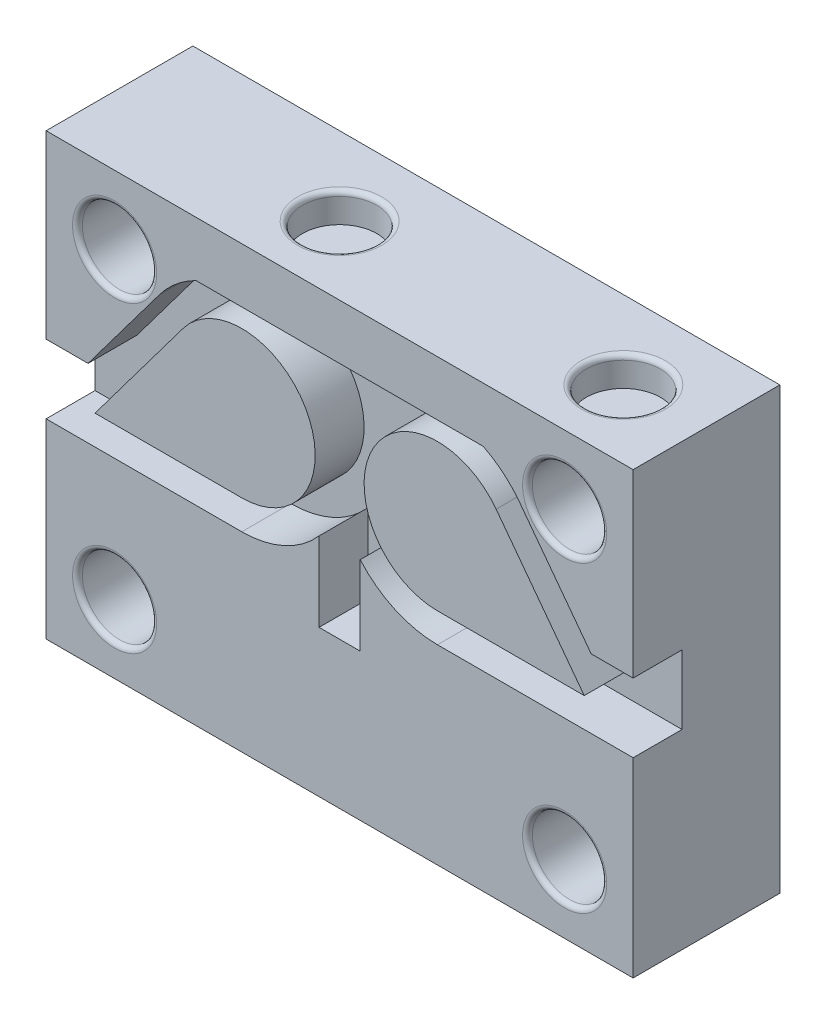
SolidWorks part; units mm, degrees
ref_plane "Front Plane" through (0, 0, 0) normal (0, 0, 1) x (1, 0, 0)
ref_plane "Top Plane" through (0, 0, 0) normal (0, 1, 0) x (1, 0, 0)
ref_plane "Right Plane" through (0, 0, 0) normal (1, 0, 0) x (0, 0, -1)
sketch "Sketch1" plane through (0, 0, 0) normal (0, 0, 1) x (1, 0, 0)
  line L0 (-37.3657, 7.5) -> (34.9105, 7.5) construction
  line L1 (-90, -22.5) -> (30, -22.5)
  line L2 (-30, -22.5) -> (-30, 22.5)
  line L3 (-30, 22.5) -> (30, 22.5)
  line L4 (30, -22.5) -> (30, 22.5)
  line L5 (-30, -22.5) -> (30, 22.5) construction
  line L6 (-30, 22.5) -> (30, -22.5) construction
  line L7 (-10, 29.4537) -> (-10, -35.1207) construction
  line L8 (0, 22.5) -> (0, -27.0967) construction
  line L9 (-10, 0) -> (-25, 0)
  line L10 (-25, 0) -> (-16, 12)
  line L11 (25, 0) -> (16, 12)
  line L12 (10, 0) -> (25, 0)
  line L13 (-50, -3) -> (-10, -3)
  line L15 (2.1006, 0.5827) -> (2.1003, -7.5128)
  line L16 (30, -16.875) -> (30, -3)
  line L17 (10, -3) -> (30, -3)
  line L18 (-10, -3) -> (-50, -3)
  line L19 (-2.1006, 0.5827) -> (-2.1006, -7.5128)
  line L20 (-2.1006, -7.5128) -> (2.1003, -7.5128)
  line L21 (-34.2857, 4.0476) -> (-25.7143, 4.0476)
  line L30 (-25.7143, 4.0476) -> (-18.4, 13.8)
  line L31 (-14.6784, 22.5) -> (-14.6784, 16.9001)
  line L32 (30, 4.0476) -> (25.7143, 4.0476)
  line L33 (25.7143, 4.0476) -> (18.4, 13.8)
  line L34 (14.6784, 22.5) -> (14.6784, 16.9001)
  line L35 (-14.6784, 16.9001) -> (14.6784, 16.9001)
  line L36 (-90, 0) -> (30, 0) construction
  line L37 (-60, 22.5) -> (-60, -27.0967) construction
  line L38 (-50, 29.4537) -> (-50, -35.1207) construction
  line L39 (-30, 22.5) -> (-90, -22.5) construction
  line L40 (-30, -22.5) -> (-90, 22.5) construction
  line L41 (-22.6343, 7.5) -> (-94.9105, 7.5) construction
  line L42 (-45.3216, 16.9001) -> (-74.6784, 16.9001)
  line L43 (-74.6784, 22.5) -> (-74.6784, 16.9001)
  line L44 (-85.7143, 4.0476) -> (-78.4, 13.8)
  line L45 (-90, 4.0476) -> (-85.7143, 4.0476)
  line L46 (-45.3216, 22.5) -> (-45.3216, 16.9001)
  line L47 (-34.2857, 4.0476) -> (-41.6, 13.8)
  line L48 (-57.8994, -7.5128) -> (-62.1003, -7.5128)
  line L49 (-57.8994, 0.5827) -> (-57.8994, -7.5128)
  line L50 (-70, -3) -> (-90, -3)
  line L51 (-90, -16.875) -> (-90, -3)
  line L52 (-62.1006, 0.5827) -> (-62.1003, -7.5128)
  line L53 (-70, 0) -> (-85, 0)
  line L54 (-85, 0) -> (-76, 12)
  line L55 (-35, 0) -> (-44, 12)
  line L56 (-50, 0) -> (-35, 0)
  line L57 (-90, -22.5) -> (-90, 22.5)
  line L58 (-30, 22.5) -> (-90, 22.5)
  circle A0 centre (-10, 7.5) radius 7.5
  circle A1 centre (10, 7.5) radius 7.5
  arc A2 (2.1006, 0.5827) -> (10, -3) centre (10, 7.5) ccw
  arc A3 (-2.1006, 0.5827) -> (-10, -3) centre (-10, 7.5) cw
  arc A4 (-18.4, 13.8) -> (-14.6784, 16.9001) centre (-10, 7.5) cw
  arc A5 (18.4, 13.8) -> (14.6784, 16.9001) centre (10, 7.5) ccw
  circle A6 centre (-23, 15.5) radius 3.8
  circle A7 centre (23, 15.5) radius 3.8
  circle A8 centre (23, -15.5) radius 3.8
  circle A9 centre (-23, -15.5) radius 3.8
  circle A10 centre (-37, -15.5) radius 3.8
  circle A11 centre (-83, -15.5) radius 3.8
  circle A12 centre (-83, 15.5) radius 3.8
  circle A13 centre (-37, 15.5) radius 3.8
  arc A14 (-78.4, 13.8) -> (-74.6784, 16.9001) centre (-70, 7.5) cw
  arc A15 (-41.6, 13.8) -> (-45.3216, 16.9001) centre (-50, 7.5) ccw
  arc A16 (-57.8994, 0.5827) -> (-50, -3) centre (-50, 7.5) ccw
  arc A17 (-62.1006, 0.5827) -> (-70, -3) centre (-70, 7.5) cw
  circle A18 centre (-70, 7.5) radius 7.5
  circle A19 centre (-50, 7.5) radius 7.5
  point P0 (0, 0)
  point P53 (-30, 0)
  point P86 (-30, 4.0476)
  point P90 (-30, -3)
  point P96 (-60, 0)
  dimension "D5" = 15
  dimension "D8" = 10.5
  dimension "D24" = 15.3216
  dimension "D7" = 7.6
  dimension "D2" = 45
  dimension "D3" = 15
  dimension "D4" = 20
  dimension "D6" = 15
  dimension "D9" = 7
  dimension "D10" = 7
  dimension "D11" = 60
  dimension "D12" = 4.2009
  dimension "D13" = 8.0954
  dimension "D20" = 3
  dimension "D21" = 10.5
  dimension "D23" = 4.2857
extrude "Boss-Extrude3" add sketch "Sketch1" along normal blind 15 contours L30 A4 L31 L3 L2 L21 A6 | L31 L35 L34 L3 | A5 L33 L32 L4 L3 L34 A7 | L19 A3 L13 L2 L1 L4 L17 A2 L15 L20 A8 A9 | A0 | A0 L10 L9 | A1 | L11 A1 L12 region at (0, -12.4766, 0) region at (-29.7602, 13.2738, 0) region at (27.8571, 4.2875, 0) region at (0, 19.7001, 0) region at (-18.9601, 3.02, 0) region at (-10, 7.5, 0) region at (18.9601, 3.02, 0) region at (10, 7.5, 0)
extrude "Boss-Extrude4" add sketch "Sketch1<10>" along normal blind 10 contours L33 A5 L35 A4 L30 L21 L2 L13 A3 L19 L20 L15 A2 L17 L4 L32 A0 L9 L10 L12 A1 L11 region at (0, 4.9915, 0)
sketch "Sketch1<10>" plane through (0, 0, 0) normal (0, 0, 1) x (1, 0, 0) same geometry as "Sketch1"
sketch "Sketch3" plane through (0, 22.5, 0) normal (0, 1, 0) x (1, 0, 0)
  line L0 (30, -15) -> (30, 0) construction
  line L1 (-30, 0) -> (30, 0) construction
  circle A0 centre (22, -8) radius 3.8
  circle A1 centre (-7, -8) radius 3.8
  dimension "D3" = 7.6
  dimension "D5" = 7.6
  dimension "D1" = 8
  dimension "D2" = 8
  dimension "D4" = 8
  dimension "D6" = 29
extrude "Cut-Extrude2" cut sketch "Sketch3" against normal blind 3
fillet "Fillet2" radius 0.5 10 edges at (26.8, 15.5, 0) (26.8, -15.5, 0) (-19.2, 15.5, 0) (-19.2, -15.5, 0) (-19.2, 15.5, 15) (-19.2, -15.5, 15) (26.8, -15.5, 15) (26.8, 15.5, 15) (22, 22.5, 11.8) (-7, 22.5, 11.8)
